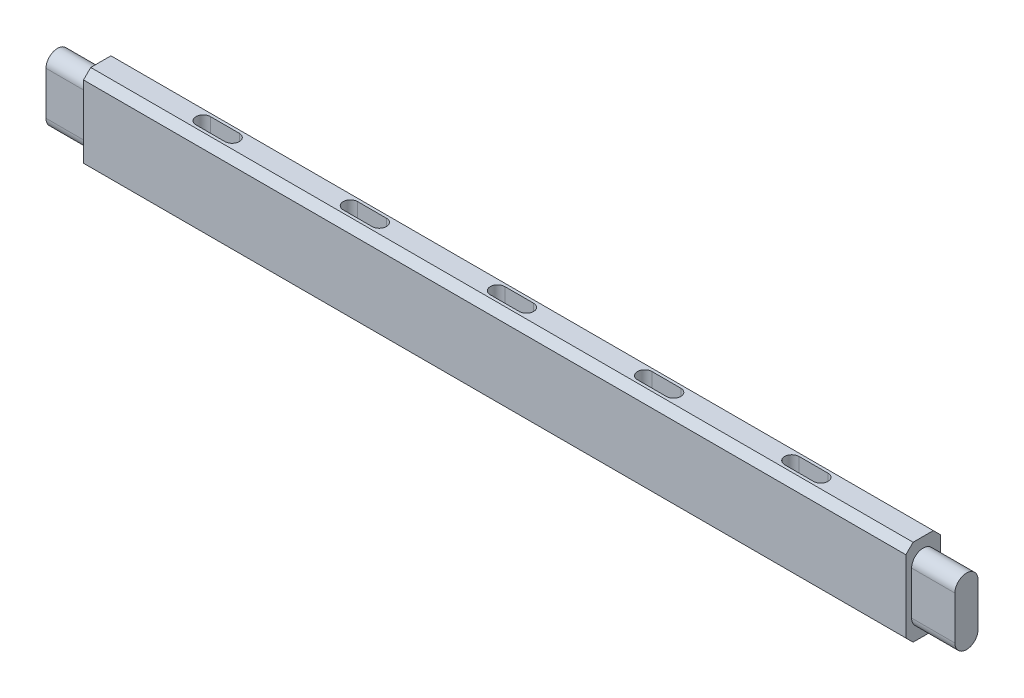
SolidWorks part; units mm, degrees
ref_plane "Front" through (0, 0, 0) normal (0, 0, 1) x (1, 0, 0)
ref_plane "Top" through (0, 0, 0) normal (0, 1, 0) x (1, 0, 0)
ref_plane "Right" through (0, 0, 0) normal (1, 0, 0) x (0, 0, -1)
sketch "Esquisse1" plane through (0, 0, 0) normal (0, 0, 1) x (1, 0, 0)
  line L1 (0, 0) -> (570, 0)
  line L2 (0, 0) -> (0, 60)
  line L3 (0, 60) -> (570, 60)
  line L4 (570, 0) -> (570, 60)
  dimension "D1" = 570
  dimension "D2" = 60
extrude "Boss.-Extru.1" add sketch "Esquisse1" along normal blind 24
sketch "Esquisse2" plane through (0, 0, 0) normal (-1, 0, 0) x (0, 0, 1)
  line L0 (12, 0) -> (12, 60) construction
  line L1 (24, 0) -> (0, 0) construction
  line L2 (24, 60) -> (0, 60) construction
  line L3 (12, 15) -> (12, 45) construction
  line L4 (4, 15) -> (4, 45)
  line L5 (20, 15) -> (20, 45)
  arc A0 (4, 15) -> (20, 15) centre (12, 15) ccw
  arc A1 (20, 45) -> (4, 45) centre (12, 45) ccw
  point P8 (12, 30)
  dimension "D1" = 16
  dimension "D2" = 30
extrude "Boss.-Extru.2" add sketch "Esquisse2" along normal blind 30
extrude "Boss.-Extru.3" add sketch "Esquisse2<2>" against normal blind 30 from vertex starting at point (570, 60, 0)
sketch "Esquisse2<2>" plane through (0, 0, 0) normal (-1, 0, 0) x (0, 0, 1) same geometry as "Esquisse2"
chamfer "Chanfrein1" distance 5 angle 45 4 edges at (285, 0, 24) (285, 0, 0) (285, 60, 0) (285, 60, 24)
sketch "Esquisse3" [suppressed] plane through (0, 60, 0) normal (0, 1, 0) x (1, 0, 0)
  line L0 (591, -19) -> (591, -5) construction
  line L1 (0, -19) -> (1182, -19) construction
  line L2 (591, -12) -> (693, -12) construction
  line L3 (642, -12) -> (642, -5) construction
  line L4 (1182, -5) -> (0, -5) construction
  line L7 (591, -12) -> (489, -12) construction
  line L8 (479, -12) -> (499, -12) construction
  line L9 (479, -7) -> (499, -7)
  line L10 (479, -17) -> (499, -17)
  line L11 (377, -12) -> (397, -12) construction
  line L12 (377, -7) -> (397, -7)
  line L13 (377, -17) -> (397, -17)
  line L14 (275, -12) -> (295, -12) construction
  line L15 (275, -7) -> (295, -7)
  line L16 (275, -17) -> (295, -17)
  line L17 (173, -12) -> (193, -12) construction
  line L18 (173, -7) -> (193, -7)
  line L19 (173, -17) -> (193, -17)
  line L20 (71, -12) -> (91, -12) construction
  line L21 (71, -7) -> (91, -7)
  line L22 (71, -17) -> (91, -17)
  line L23 (595, -16) -> (601, -12) construction
  line L24 (595, -16) -> (601, -12) construction
  line L25 (581, -12) -> (601, -12) construction
  line L26 (581, -7) -> (601, -7)
  line L27 (581, -17) -> (601, -17)
  line L29 (1111, -12) -> (1091, -12) construction
  line L30 (1111, -7) -> (1091, -7)
  line L31 (1111, -17) -> (1091, -17)
  line L32 (1009, -12) -> (989, -12) construction
  line L33 (1009, -7) -> (989, -7)
  line L34 (1009, -17) -> (989, -17)
  line L35 (907, -12) -> (887, -12) construction
  line L36 (907, -7) -> (887, -7)
  line L37 (907, -17) -> (887, -17)
  line L38 (805, -12) -> (785, -12) construction
  line L39 (805, -7) -> (785, -7)
  line L40 (805, -17) -> (785, -17)
  line L41 (703, -12) -> (683, -12) construction
  line L42 (703, -7) -> (683, -7)
  line L43 (703, -17) -> (683, -17)
  line L113 (-32, -12) -> (-12, -12) construction
  line L114 (-32, -7) -> (-12, -7)
  line L115 (-32, -17) -> (-12, -17)
  line L116 (-31, -12) -> (-11, -12) construction
  line L117 (-31, -7) -> (-11, -7)
  line L118 (-31, -17) -> (-11, -17)
  arc A0 (479, -7) -> (479, -17) centre (479, -12) ccw
  arc A1 (499, -17) -> (499, -7) centre (499, -12) ccw
  arc A2 (377, -7) -> (377, -17) centre (377, -12) ccw
  arc A3 (397, -17) -> (397, -7) centre (397, -12) ccw
  arc A4 (275, -7) -> (275, -17) centre (275, -12) ccw
  arc A5 (295, -17) -> (295, -7) centre (295, -12) ccw
  arc A6 (173, -7) -> (173, -17) centre (173, -12) ccw
  arc A7 (193, -17) -> (193, -7) centre (193, -12) ccw
  arc A8 (71, -7) -> (71, -17) centre (71, -12) ccw
  arc A9 (91, -17) -> (91, -7) centre (91, -12) ccw
  arc A10 (581, -7) -> (581, -17) centre (581, -12) ccw
  arc A11 (601, -17) -> (601, -7) centre (601, -12) ccw
  arc A14 (1111, -7) -> (1111, -17) centre (1111, -12) cw
  arc A15 (1091, -17) -> (1091, -7) centre (1091, -12) cw
  arc A16 (1009, -7) -> (1009, -17) centre (1009, -12) cw
  arc A17 (989, -17) -> (989, -7) centre (989, -12) cw
  arc A18 (907, -7) -> (907, -17) centre (907, -12) cw
  arc A19 (887, -17) -> (887, -7) centre (887, -12) cw
  arc A20 (805, -7) -> (805, -17) centre (805, -12) cw
  arc A21 (785, -17) -> (785, -7) centre (785, -12) cw
  arc A22 (703, -7) -> (703, -17) centre (703, -12) cw
  arc A23 (683, -17) -> (683, -7) centre (683, -12) cw
  arc A72 (-31, -7) -> (-31, -17) centre (-31, -12) ccw
  arc A73 (-11, -17) -> (-11, -7) centre (-11, -12) ccw
  point P10 (489, -12)
  point P19 (387, -12)
  point P26 (285, -12)
  point P33 (183, -12)
  point P40 (81, -12)
  point P49 (591, -12)
  point P59 (1101, -12)
  point P66 (999, -12)
  point P73 (897, -12)
  point P80 (795, -12)
  point P87 (693, -12)
  point P94 (-11, -16)
  point P104 (-11, -16)
  point P111 (-11, -16)
  point P118 (-11, -16)
  point P125 (-16, -16)
  point P132 (-16, -16)
  point P139 (-16, -16)
  point P146 (-16, -16)
  point P153 (-55, -16)
  point P160 (-55, -16)
  point P167 (-55, -16)
  point P174 (-55, -16)
  point P181 (-55, -16)
  point P188 (-55, -16)
  point P195 (-55, -16)
  point P202 (-55, -16)
  point P209 (-320, -16)
  point P216 (-320, -16)
  point P223 (-19, -12)
  point P230 (-19, -12)
  point P237 (-34, -12)
  point P244 (-34, -12)
  point P251 (-22, -12)
  point P258 (-22, -12)
  point P265 (-21, -12)
  dimension "D1" = 10
  dimension "D2" = 204
  dimension "D3" = 20
  dimension "D4" = 6
  dimension "D5" = 102
extrude "Enlèv. mat.-Extru.1" [suppressed] cut sketch "Esquisse3" against normal blind 15
sketch "Esquisse5" plane through (0, 60, 0) normal (0, 1, 0) x (1, 0, 0)
  line L0 (285, -47.719) -> (285, 23.719) construction
  line L1 (0, 0) -> (570, 0) construction
  line L2 (285, -12) -> (387, -12) construction
  line L3 (336, -12) -> (336, -5) construction
  line L4 (570, -5) -> (0, -5) construction
  line L6 (285, -5) -> (285, 23.719) construction
  line L7 (285, -12) -> (183, -12) construction
  line L8 (173, -12) -> (193, -12) construction
  line L9 (173, -7) -> (193, -7)
  line L10 (173, -17) -> (193, -17)
  line L11 (71, -12) -> (91, -12) construction
  line L12 (71, -7) -> (91, -7)
  line L13 (71, -17) -> (91, -17)
  line L23 (419.8491, -12) -> (295, -12) construction
  line L24 (419.8491, -12) -> (295, -12) construction
  line L25 (275, -12) -> (295, -12) construction
  line L26 (275, -7) -> (295, -7)
  line L27 (275, -17) -> (295, -17)
  line L38 (499, -12) -> (479, -12) construction
  line L39 (499, -7) -> (479, -7)
  line L40 (499, -17) -> (479, -17)
  line L41 (397, -12) -> (377, -12) construction
  line L42 (397, -7) -> (377, -7)
  line L43 (397, -17) -> (377, -17)
  line L485 (-26, -12) -> (-6, -12) construction
  line L486 (-26, -7) -> (-6, -7)
  line L487 (-26, -17) -> (-6, -17)
  line L488 (-128, -12) -> (-108, -12) construction
  line L489 (-128, -7) -> (-108, -7)
  line L490 (-128, -17) -> (-108, -17)
  line L491 (-230, -12) -> (-210, -12) construction
  line L492 (-230, -7) -> (-210, -7)
  line L493 (-230, -17) -> (-210, -17)
  line L494 (-332, -12) -> (-312, -12) construction
  line L495 (-332, -7) -> (-312, -7)
  line L496 (-332, -17) -> (-312, -17)
  line L497 (-31, -12) -> (-11, -12) construction
  line L498 (-31, -7) -> (-11, -7)
  line L499 (-31, -17) -> (-11, -17)
  line L500 (-133, -12) -> (-113, -12) construction
  line L501 (-133, -7) -> (-113, -7)
  line L502 (-133, -17) -> (-113, -17)
  line L503 (-235, -12) -> (-215, -12) construction
  line L504 (-235, -7) -> (-215, -7)
  line L505 (-235, -17) -> (-215, -17)
  line L506 (-337, -12) -> (-317, -12) construction
  line L507 (-337, -7) -> (-317, -7)
  line L508 (-337, -17) -> (-317, -17)
  arc A0 (173, -7) -> (173, -17) centre (173, -12) ccw
  arc A1 (193, -17) -> (193, -7) centre (193, -12) ccw
  arc A2 (71, -7) -> (71, -17) centre (71, -12) ccw
  arc A3 (91, -17) -> (91, -7) centre (91, -12) ccw
  arc A10 (275, -7) -> (275, -17) centre (275, -12) ccw
  arc A11 (295, -17) -> (295, -7) centre (295, -12) ccw
  arc A20 (499, -7) -> (499, -17) centre (499, -12) cw
  arc A21 (479, -17) -> (479, -7) centre (479, -12) cw
  arc A22 (397, -7) -> (397, -17) centre (397, -12) cw
  arc A23 (377, -17) -> (377, -7) centre (377, -12) cw
  arc A326 (-31, -7) -> (-31, -17) centre (-31, -12) ccw
  arc A327 (-11, -17) -> (-11, -7) centre (-11, -12) ccw
  arc A328 (-133, -7) -> (-133, -17) centre (-133, -12) ccw
  arc A329 (-113, -17) -> (-113, -7) centre (-113, -12) ccw
  arc A330 (-235, -7) -> (-235, -17) centre (-235, -12) ccw
  arc A331 (-215, -17) -> (-215, -7) centre (-215, -12) ccw
  arc A332 (-337, -7) -> (-337, -17) centre (-337, -12) ccw
  arc A333 (-317, -17) -> (-317, -7) centre (-317, -12) ccw
  point P10 (183, -12)
  point P19 (81, -12)
  point P26 (-169, -16.4919)
  point P33 (-272, -16.4919)
  point P49 (285, -12)
  point P55 (-66, -16.4919)
  point P80 (489, -12)
  point P87 (387, -12)
  point P94 (-225.2423, -16.4919)
  point P104 (-225.2423, -16.4919)
  point P111 (-225.2423, -16.4919)
  point P118 (-225.2423, -16.4919)
  point P125 (-230.2423, -16.4919)
  point P132 (-230.2423, -16.4919)
  point P139 (-230.2423, -16.4919)
  point P146 (-230.2423, -16.4919)
  point P153 (-269.2423, -16.4919)
  point P160 (-269.2423, -16.4919)
  point P167 (-269.2423, -16.4919)
  point P174 (-269.2423, -16.4919)
  point P181 (-269.2423, -16.4919)
  point P188 (-269.2423, -16.4919)
  point P195 (-269.2423, -16.4919)
  point P202 (-269.2423, -16.4919)
  point P209 (-534.2423, -16.4919)
  point P216 (-534.2423, -16.4919)
  point P223 (-375, -16.4919)
  point P230 (-66, -16.4919)
  point P237 (-169, -16.4919)
  point P244 (-272, -16.4919)
  point P251 (-375, -16.4919)
  point P258 (-66, -16.4919)
  point P265 (-169, -16.4919)
  point P272 (-272, -16.4919)
  point P279 (-375, -16.4919)
  point P286 (-66, -16.4919)
  point P293 (-169, -16.4919)
  point P300 (-272, -16.4919)
  point P307 (-375, -16.4919)
  point P314 (-66, -16.4919)
  point P321 (-169, -16.4919)
  point P328 (-272, -16.4919)
  point P335 (-375, -16.4919)
  point P342 (-66, -16.4919)
  point P349 (-169, -16.4919)
  point P356 (-272, -16.4919)
  point P363 (-375, -16.4919)
  point P370 (-66, -16.4919)
  point P377 (-169, -16.4919)
  point P384 (-272, -16.4919)
  point P391 (-375, -16.4919)
  point P398 (-66, -16.4919)
  point P405 (-169, -16.4919)
  point P412 (-272, -16.4919)
  point P419 (-375, -16.4919)
  point P426 (-66, -16.4919)
  point P433 (-169, -16.4919)
  point P440 (-272, -16.4919)
  point P447 (-375, -16.4919)
  point P454 (-66, -16.4919)
  point P461 (-169, -16.4919)
  point P468 (-272, -16.4919)
  point P475 (-375, -16.4919)
  point P482 (-55.5, -16.4919)
  point P489 (-158.5, -16.4919)
  point P496 (-261.5, -16.4919)
  point P503 (-364.5, -16.4919)
  point P510 (-55.5, -16.4919)
  point P517 (-158.5, -16.4919)
  point P524 (-261.5, -16.4919)
  point P531 (-364.5, -16.4919)
  point P538 (-57, -16.4919)
  point P545 (-160, -16.4919)
  point P552 (-263, -16.4919)
  point P559 (-366, -16.4919)
  point P566 (-57, -16.4919)
  point P573 (-160, -16.4919)
  point P580 (-263, -16.4919)
  point P587 (-366, -16.4919)
  point P594 (-59, -16.4919)
  point P601 (-163, -16.4919)
  point P608 (-267, -16.4919)
  point P615 (-371, -16.4919)
  point P622 (-59, -16.4919)
  point P629 (-163, -16.4919)
  point P636 (-267, -16.4919)
  point P643 (-371, -16.4919)
  point P650 (-59, -16.4919)
  point P657 (-163, -16.4919)
  point P664 (-267, -16.4919)
  point P671 (-371, -16.4919)
  point P678 (-59, -16.4919)
  point P685 (-163, -16.4919)
  point P692 (-267, -16.4919)
  point P699 (-371, -16.4919)
  point P706 (-59, -12)
  point P713 (-163, -12)
  point P720 (-267, -12)
  point P727 (-371, -12)
  point P734 (-59, -12)
  point P741 (-163, -12)
  point P748 (-267, -12)
  point P755 (-371, -12)
  point P762 (-59, -12)
  point P769 (-163, -12)
  point P776 (-267, -12)
  point P783 (-371, -12)
  point P790 (-59, -12)
  point P797 (-163, -12)
  point P804 (-267, -12)
  point P811 (-371, -12)
  point P818 (-7, -12)
  point P825 (-111, -12)
  point P832 (-215, -12)
  point P839 (-319, -12)
  point P846 (-7, -12)
  point P853 (-111, -12)
  point P860 (-215, -12)
  point P867 (-319, -12)
  point P874 (-7, -12)
  point P881 (-111, -12)
  point P888 (-215, -12)
  point P895 (-319, -12)
  point P902 (-7, -12)
  point P909 (-111, -12)
  point P916 (-215, -12)
  point P923 (-319, -12)
  point P930 (-22, -12)
  point P937 (-126, -12)
  point P944 (-230, -12)
  point P951 (-334, -12)
  point P958 (-22, -12)
  point P965 (-126, -12)
  point P972 (-230, -12)
  point P979 (-334, -12)
  point P986 (-20, -12)
  point P993 (-124, -12)
  point P1000 (-228, -12)
  point P1007 (-332, -12)
  point P1014 (-20, -12)
  point P1021 (-124, -12)
  point P1028 (-228, -12)
  point P1035 (-332, -12)
  point P1042 (-18, -12)
  point P1049 (-120, -12)
  point P1056 (-222, -12)
  point P1063 (-324, -12)
  point P1070 (-18, -12)
  point P1077 (-120, -12)
  point P1084 (-222, -12)
  point P1091 (-324, -12)
  point P1098 (-16, -12)
  point P1105 (-118, -12)
  point P1112 (-220, -12)
  point P1119 (-322, -12)
  point P1126 (-16, -12)
  point P1133 (-118, -12)
  point P1140 (-220, -12)
  point P1147 (-322, -12)
  point P1154 (-21, -12)
  point P1161 (-123, -12)
  point P1168 (-225, -12)
  point P1175 (-327, -12)
  dimension "D1" = 10
  dimension "D2" = 204
  dimension "D3" = 20
  dimension "D4" = 6
  dimension "D5" = 102
  dimension "D6" = 12
extrude "Enlèv. mat.-Extru.2" cut sketch "Esquisse5" against normal blind 15
